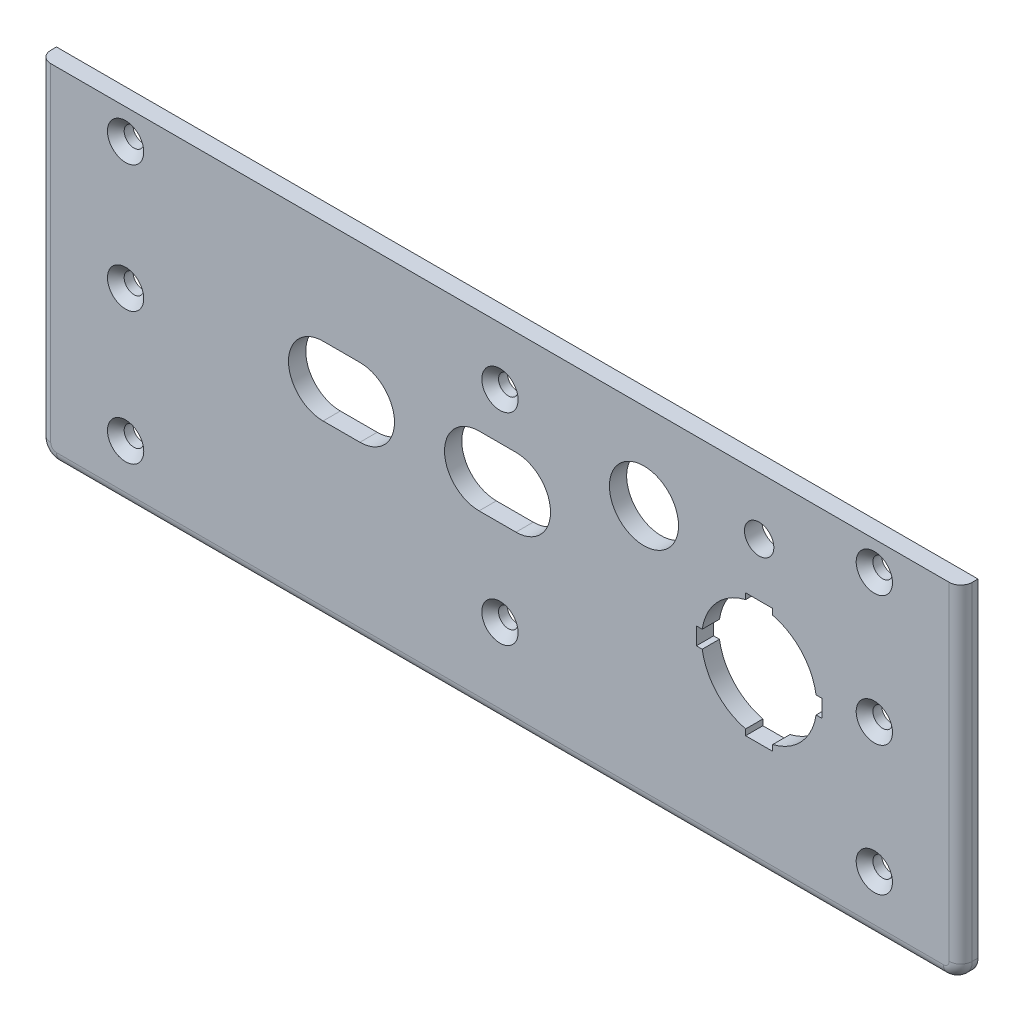
SolidWorks part; units mm, degrees
ref_plane "Front Plane" through (0, 0, 0) normal (0, 0, 1) x (1, 0, 0)
ref_plane "Top Plane" through (0, 0, 0) normal (0, 1, 0) x (1, 0, 0)
ref_plane "Right Plane" through (0, 0, 0) normal (1, 0, 0) x (0, 0, -1)
sketch "Sketch11" plane through (0, 0, 0) normal (0, 0, 1) x (1, 0, 0)
  line L0 (-44.8869, 31.5) -> (-45.8972, 31.5)
  line L1 (-45.8972, 31.5) -> (-45.8972, 28.5)
  line L2 (-45.8972, 28.5) -> (-44.8869, 28.5)
  line L3 (-35, 30) -> (-45.8972, 30) construction
  line L4 (-37.35, 20.28) -> (-37.35, 19.254)
  line L5 (-37.35, 19.254) -> (-32.65, 19.254)
  line L6 (-32.65, 19.254) -> (-32.65, 20.28)
  line L7 (-35, 30) -> (-35, 19.254) construction
  line L8 (-32.65, 40.746) -> (-32.65, 39.72)
  line L9 (-37.35, 40.746) -> (-32.65, 40.746)
  line L10 (-37.35, 39.72) -> (-37.35, 40.746)
  line L11 (-35, 18.7315) -> (-35, 30) construction
  line L12 (-25.1131, 31.5) -> (-24.1028, 31.5)
  line L13 (-24.1028, 31.5) -> (-24.1028, 28.5)
  line L14 (-24.1028, 28.5) -> (-25.1131, 28.5)
  line L15 (-35, 50) -> (-35, 30) construction
  line L17 (0, 0) -> (-160, 0)
  line L18 (0, 0) -> (0, 60)
  line L19 (0, 60) -> (-160, 60)
  line L20 (-160, 0) -> (-160, 60)
  line L21 (-83.6273, 35.9303) -> (-77.2273, 35.9303) construction
  line L22 (-83.6273, 41.9303) -> (-77.2273, 41.9303)
  line L23 (-83.6273, 29.9303) -> (-77.2273, 29.9303)
  line L24 (-110.7157, 35.9) -> (-104.3157, 35.9) construction
  line L25 (-110.7157, 41.9) -> (-104.3157, 41.9)
  line L26 (-110.7157, 29.9) -> (-104.3157, 29.9)
  arc A0 (-44.8869, 28.5) -> (-37.35, 20.28) centre (-35, 30) ccw
  circle A1 centre (-35, 30) radius 11 construction
  arc A2 (-32.65, 20.28) -> (-25.1131, 28.5) centre (-35, 30) ccw
  arc A3 (-37.35, 39.72) -> (-44.8869, 31.5) centre (-35, 30) ccw
  arc A4 (-25.1131, 31.5) -> (-32.65, 39.72) centre (-35, 30) ccw
  circle A5 centre (-35, 50) radius 2.55
  circle A6 centre (-55, 45) radius 6
  arc A7 (-103.7657, 35.9) -> (-104.3157, 36.45) centre (-104.3157, 35.9) ccw construction
  arc A8 (-110.7157, 36.45) -> (-111.2657, 35.9) centre (-110.7157, 35.9) ccw construction
  arc A9 (-76.6773, 35.9303) -> (-77.2273, 36.4803) centre (-77.2273, 35.9303) ccw construction
  arc A10 (-83.6273, 36.4803) -> (-84.1773, 35.9303) centre (-83.6273, 35.9303) ccw construction
  arc A11 (-103.7657, 35.9) -> (-104.3157, 36.45) centre (-104.3157, 35.9) ccw construction
  arc A12 (-110.7157, 36.45) -> (-111.2657, 35.9) centre (-110.7157, 35.9) ccw construction
  arc A13 (-76.6773, 35.9303) -> (-77.2273, 36.4803) centre (-77.2273, 35.9303) ccw construction
  arc A14 (-83.6273, 36.4803) -> (-84.1773, 35.9303) centre (-83.6273, 35.9303) ccw construction
  arc A15 (-83.6273, 41.9303) -> (-83.6273, 29.9303) centre (-83.6273, 35.9303) ccw
  arc A16 (-77.2273, 29.9303) -> (-77.2273, 41.9303) centre (-77.2273, 35.9303) ccw
  arc A17 (-110.7157, 41.9) -> (-110.7157, 29.9) centre (-110.7157, 35.9) ccw
  arc A18 (-104.3157, 29.9) -> (-104.3157, 41.9) centre (-104.3157, 35.9) ccw
  point P42 (-80.4273, 35.9303)
  point P47 (-107.5157, 35.9)
  dimension "D1" = 20
  dimension "D4" = 22
  dimension "D5" = 5.1
  dimension "D11" = 12
  dimension "D6" = 20
  dimension "D2" = 3
  dimension "D3" = 4.7
  dimension "D7" = 160
  dimension "D8" = 35
  dimension "D9" = 30
  dimension "D10" = 60
  dimension "D12" = 20
  dimension "D13" = 12
  dimension "D14" = 15
extrude "Boss-Extrude1" add sketch "Sketch11" along normal blind 3 contours L20 L17 L18 L19 A5 A4 L12 L13 L14 A2 L6 L5 L4 A0 L2 L1 L0 A3 L10 L9 L8 region at (-81.5053, 29.5032, 0)
fillet "Fillet1" radius 2 3 edges at (-80, 0, 3) (-160, 30, 3) (0, 30, 3)
fillet "Fillet3" radius 3 4 edges at (-0.5858, 0.5858, 2.4142) (-159.4142, 0.5858, 2.4142) (-160, 0, 0.5) (0, 0, 0.5)
sketch "Sketch12" plane through (0, 0, 3) normal (0, 0, 1) x (1, 0, 0)
  line L1 (-80, 50) -> (-80, 60) construction
  line L2 (-2, 60) -> (-158, 60) construction
  circle A0 centre (-145, 9.7713) radius 3 construction
  circle A1 centre (-145, 32.7287) radius 3 construction
  circle A2 centre (-145, 54.7713) radius 3 construction
  circle A3 centre (-15, 10) radius 3 construction
  circle A4 centre (-15, 32.5) radius 3 construction
  circle A5 centre (-15, 55) radius 3 construction
  circle A6 centre (-145, 9.7713) radius 3
  circle A7 centre (-145, 32.7287) radius 3
  circle A8 centre (-145, 54.7713) radius 3
  circle A9 centre (-15, 10) radius 3
  circle A10 centre (-15, 32.5) radius 3
  circle A11 centre (-15, 55) radius 3
  circle A12 centre (-80, 50) radius 3
  circle A13 centre (-80, 15) radius 3
  circle A14 centre (-80, 50) radius 3 construction
  circle A15 centre (-80, 15) radius 3 construction
hole_wizard "CSK for M3 Flat Head Machine Screw1" positions "3DSketch1" profile "Sketch13" countersink size "M3" standard "ANSI Metric" end condition through all
sketch3d "3DSketch1"
  point P0 (-145, 54.7713, 3)
  point P3 (-145, 32.7287, 3)
  point P6 (-145, 9.7713, 3)
  point P9 (-15, 10, 3)
  point P12 (-15, 32.5, 3)
  point P15 (-15, 55, 3)
  point P18 (-80, 50, 3)
  point P21 (-80, 15, 3)
sketch "Sketch13" plane through (-145, 54.7713, 3) normal (1, 0, 0) x (0, -1, 0)
  line L0 (0, 0) -> (0, 3)
  line L1 (0, 3) -> (1.7, 3)
  line L2 (1.7, 3) -> (1.7, 1.45)
  line L3 (1.7, 1.45) -> (3.15, 0)
  line L5 (3.15, 0) -> (0, 0)
  line L6 (-1.7, 1.45) -> (-3.15, 0) construction
  line L11 (0, -6.35) -> (0, 107.95) construction
  dimension "Thru Hole Dia." = 3.4
  dimension "Thru Hole Depth" = 3
  dimension "Near C'Sink Dia." = 6.3
  dimension "Near C'Sink Angle" = 90
